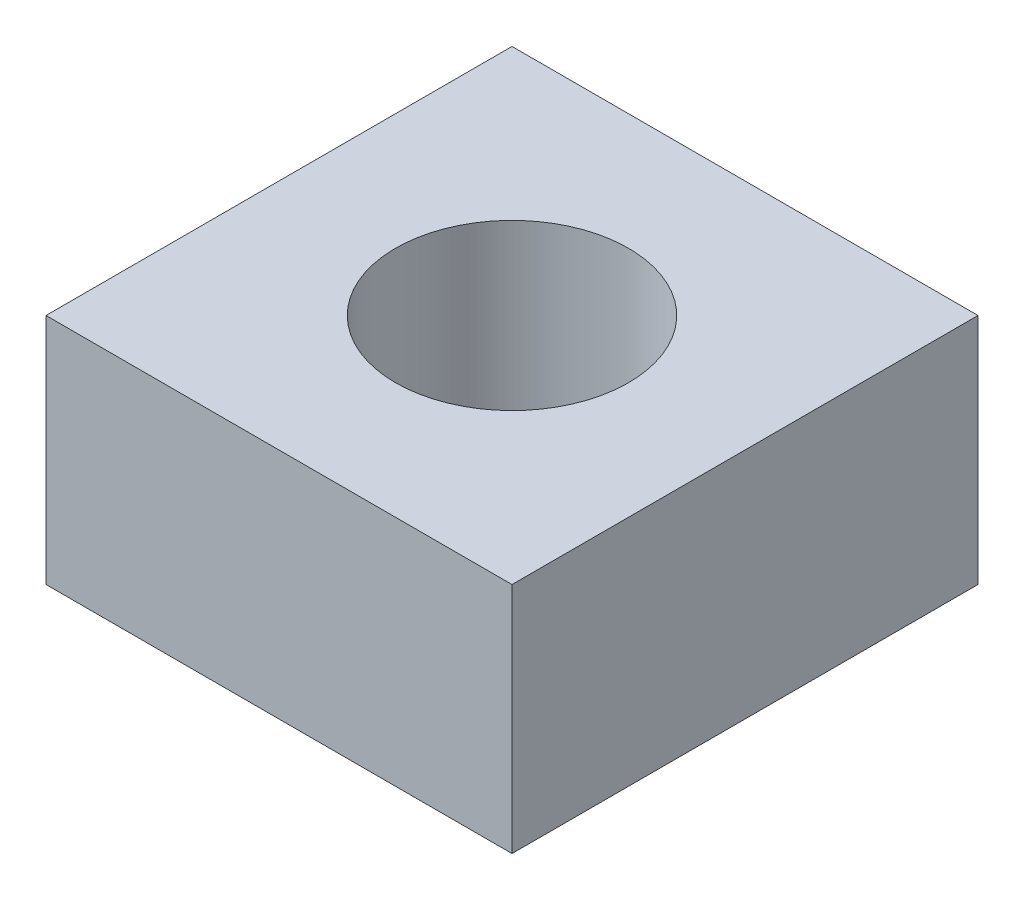
SolidWorks part; units mm, degrees
material "6061-T6 (SS)"
ref_plane "Front Plane" through (0, 0, 0) normal (0, 0, 1) x (1, 0, 0)
ref_plane "Top Plane" through (0, 0, 0) normal (0, 1, 0) x (1, 0, 0)
ref_plane "Right Plane" through (0, 0, 0) normal (1, 0, 0) x (0, 0, -1)
ref_axis "Axis1" through (0, 0, 55) along (0, 0, -1)
sketch "Sketch1" plane through (0, 0, 0) normal (0, 1, 0) x (1, 0, 0)
  line L1 (-10, 10) -> (10, 10)
  line L2 (-10, 10) -> (-10, -10)
  line L3 (-10, -10) -> (10, -10)
  line L4 (10, 10) -> (10, -10)
  line L5 (-10, 10) -> (10, -10) construction
  line L6 (-10, -10) -> (10, 10) construction
  circle A0 centre (0, 0) radius 5
  point P0 (0, 0)
  dimension "D2" = 10
  dimension "D1" = 20
extrude "Boss-Extrude1" add sketch "Sketch1" along normal blind 10
